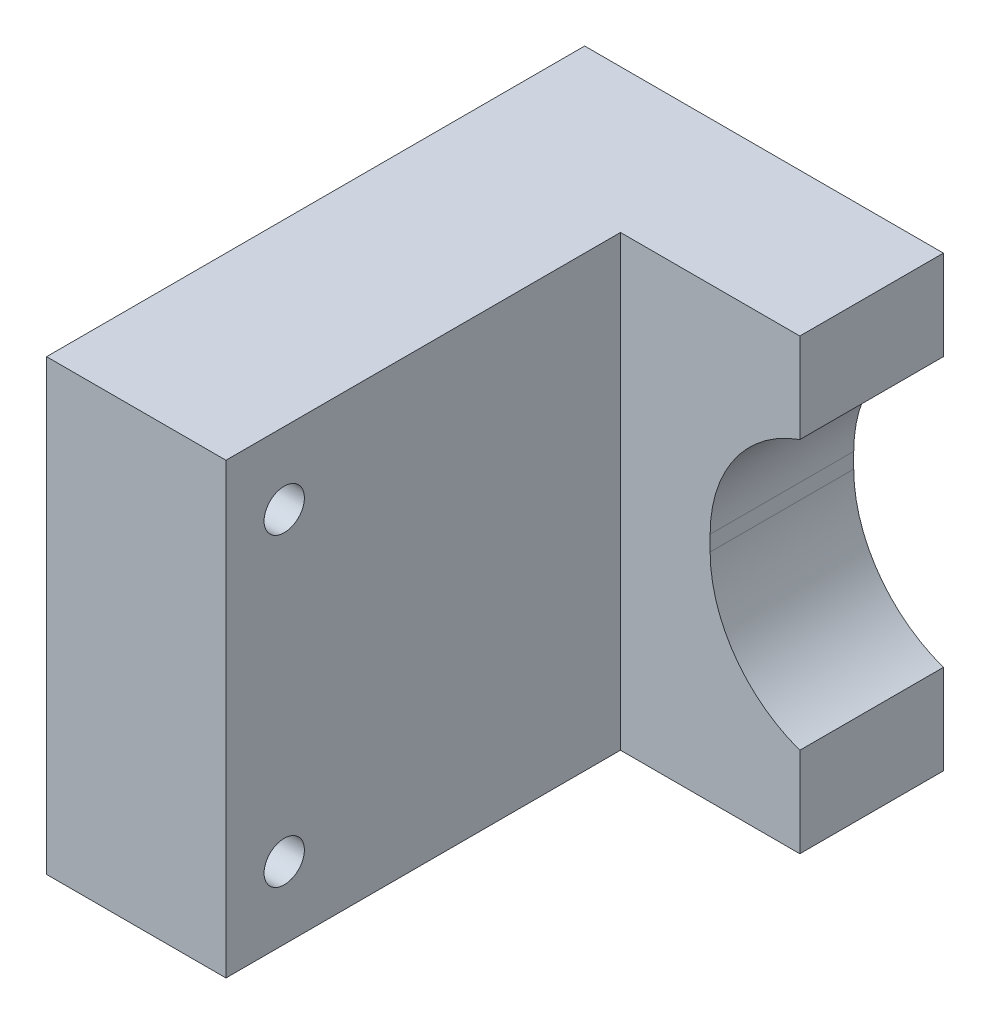
SolidWorks part; units mm, degrees
ref_plane "Front Plane" through (0, 0, 0) normal (0, 0, 1) x (1, 0, 0)
ref_plane "Top Plane" through (0, 0, 0) normal (0, 1, 0) x (1, 0, 0)
ref_plane "Right Plane" through (0, 0, 0) normal (1, 0, 0) x (0, 0, -1)
sketch "Sketch3" plane through (0, 0, 0) normal (0, 1, 0) x (1, 0, 0)
  line L1 (10, -30) -> (-10, -30)
  line L2 (10, -30) -> (10, 30)
  line L3 (10, 30) -> (-10, 30)
  line L4 (-10, -30) -> (-10, 30)
  line L5 (10, -30) -> (-10, 30) construction
  line L6 (10, 30) -> (-10, -30) construction
  line L7 (10, 30) -> (30, 30)
  line L8 (10, 30) -> (10, 13.9904)
  line L9 (10, 13.9904) -> (30, 13.9904)
  line L10 (30, 30) -> (30, 13.9904)
  point P0 (0, 0)
  dimension "D1" = 60
  dimension "D2" = 20
  dimension "D3" = 20
extrude "Boss-Extrude1" add sketch "Sketch3" along normal blind 50 contours L4 L1 L2 L3 | L10 L7 L2 L9 region at (0, 0, 0) region at (20, 0, -21.9952)
sketch "Sketch4" plane through (30, 0, 0) normal (1, 0, 0) x (0, 0, -1)
  line L0 (13.9904, 50) -> (13.9904, 0) construction
  line L1 (13.9904, 40) -> (30, 40)
  line L2 (13.9904, 40) -> (13.9904, 10)
  line L3 (13.9904, 10) -> (30, 10)
  line L4 (30, 40) -> (30, 10)
  line L5 (30, 50) -> (30, 0) construction
  dimension "D1" = 30
  dimension "D2" = 10
extrude "Cut-Extrude1" cut sketch "Sketch4" against normal blind 10
fillet "Fillet4" radius 15 2 edges at (20, 10, -21.9952) (20, 40, -21.9952)
hole_wizard "CSK for #8 Flat Head Machine Screw (100)1" positions "Sketch5" profile "Sketch6" countersink size "#8" standard "ANSI Inch" end condition up to next
sketch "Sketch5" plane through (-10, 0, 0) normal (-1, 0, 0) x (0, 0, 1)
  line L0 (30, 0) -> (-30, 0) construction
  line L1 (30, 50) -> (30, 0) construction
  line L2 (30, 50) -> (-30, 50) construction
  point P0 (23.5, 8)
  point P2 (23.5, 42)
  dimension "D1" = 8
  dimension "D2" = 6.5
  dimension "D3" = 6.5
  dimension "D4" = 8
sketch "Sketch6" plane through (-10, 8, 23.5) normal (0, 1, 0) x (0, 0, 1)
  line L0 (0, 0) -> (0, 20)
  line L1 (0, 20) -> (2.2479, 20)
  line L2 (2.2479, 20) -> (2.2479, 1.6518)
  line L3 (2.2479, 1.6518) -> (4.2164, 0)
  line L5 (4.2164, 0) -> (0, 0)
  line L6 (-2.2479, 1.6518) -> (-4.2164, 0) construction
  line L11 (0, -6.35) -> (0, 107.95) construction
  dimension "Thru Hole Dia." = 4.4958
  dimension "Thru Hole Depth" = 20
  dimension "Near C'Sink Dia." = 8.4328
  dimension "Near C'Sink Angle" = 100
sketch "Sketch7" plane through (0, 0, -30) normal (0, 0, -1) x (-1, 0, 0)
  line L0 (10, 50) -> (10, 0) construction
  line L1 (7, 15) -> (-3, 15)
  line L2 (7, 15) -> (7, 35)
  line L3 (7, 35) -> (-3, 35)
  line L4 (-3, 15) -> (-3, 35)
  line L6 (-30, 50) -> (10, 50) construction
  dimension "D1" = 3
  dimension "D2" = 10
  dimension "D3" = 15
  dimension "D4" = 20
extrude "Cut-Extrude2" cut sketch "Sketch7" against normal blind 50
sketch "Sketch8" plane through (-10, 0, 0) normal (-1, 0, 0) x (0, 0, 1)
  line L0 (30, 50) -> (-30, 50) construction
  line L1 (20, 15) -> (10, 15)
  line L2 (20, 15) -> (20, 35)
  line L3 (20, 35) -> (10, 35)
  line L4 (10, 15) -> (10, 35)
  line L5 (-30, 50) -> (-30, 0) construction
  dimension "D1" = 20
  dimension "D2" = 15
  dimension "D3" = 10
  dimension "D4" = 50
extrude "Cut-Extrude3" cut sketch "Sketch8" against normal blind 13 contours L4 L3 L2 L1
